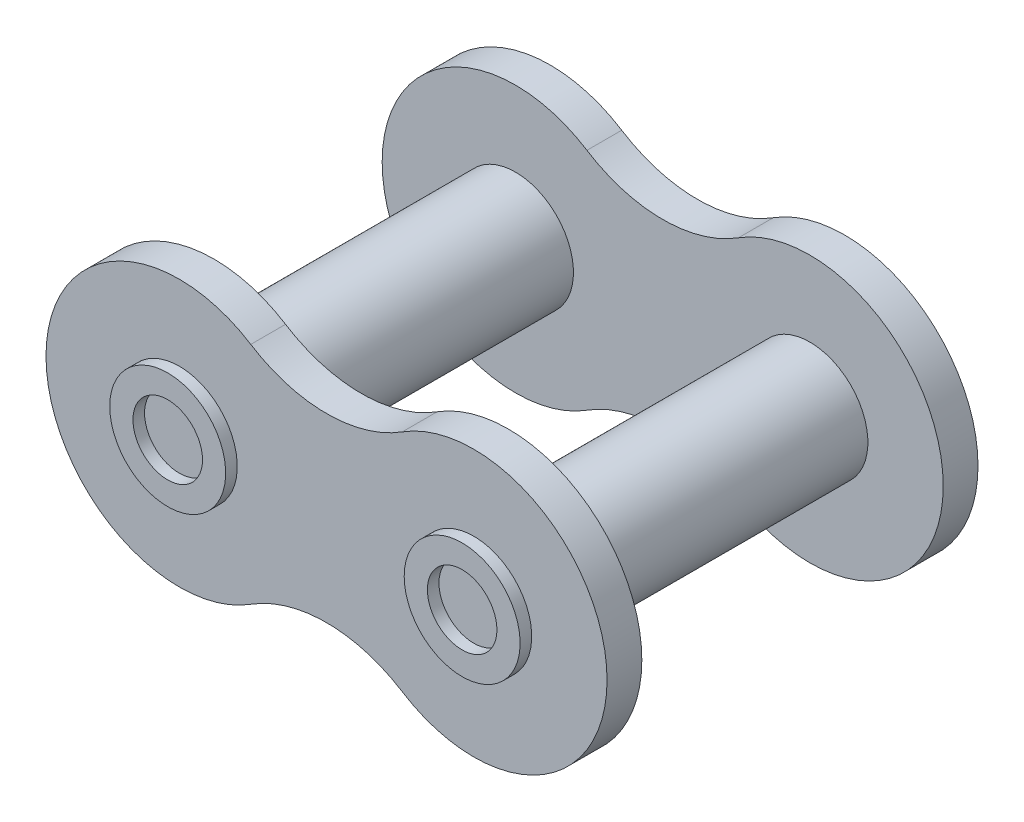
SolidWorks part; units mm, degrees
note: The reader was unsure of these and kept them because the rebuilt part matched: shared geometry of "Sketch1<5>".
ref_plane "Front Plane" through (0, 0, 0) normal (0, 0, 1) x (1, 0, 0)
ref_plane "Top Plane" through (0, 0, 0) normal (0, 1, 0) x (1, 0, 0)
ref_plane "Right Plane" through (0, 0, 0) normal (1, 0, 0) x (0, 0, -1)
sketch "Sketch1" plane through (0, 0, 0) normal (0, 0, 1) x (1, 0, 0)
  line L0 (0, 0) -> (-6.35, 0) construction
  line L1 (0, 0) -> (0, 10) construction
  circle A0 centre (-6.35, 0) radius 2.5
  circle A1 centre (6.35, 0) radius 2.5
  arc A2 (-3.2677, 4.854) -> (-3.2677, -4.854) centre (-6.35, 0) ccw
  arc A3 (3.2677, 4.854) -> (3.2677, -4.854) centre (6.35, 0) cw
  arc A4 (-3.2677, 4.854) -> (3.2677, 4.854) centre (0, 10) ccw
  arc A5 (-3.2677, -4.854) -> (3.2677, -4.854) centre (0, -10) cw
  circle A6 centre (-6.35, 0) radius 5.75 construction
  dimension "D2" = 5
  dimension "D3" = 5.75
  dimension "D1" = 12.7
  dimension "D4" = 10
extrude "Boss-Extrude3" add sketch "Sketch1" along normal mid plane 13 contours A1 | A0
extrude "Boss-Extrude7" add sketch "Sketch1<5>" against normal blind 1.5 from offset 6.5 contours A2 A5 A3 A4 offset against normal yes
sketch "Sketch1<5>" plane through (0, 0, 0) normal (0, 0, 1) x (1, 0, 0) same geometry as "Sketch1"
mirror "Mirror1" about plane through (0, 0, 0) normal (0, 0, 1) of "Boss-Extrude7"
sketch "Sketch2" plane through (0, 0, 0) normal (0, 0, 1) x (1, 0, 0)
  line L0 (0, 0) -> (0, 3.9042) construction
  circle A0 centre (-6.35, 0) radius 2.5
  arc A1 (-3.2677, 4.854) -> (3.2677, 4.854) centre (0, 10) ccw construction
  circle A2 centre (6.35, 0) radius 2.5
  dimension "D1" = 5
extrude "Boss-Extrude8" add sketch "Sketch2" along normal offset from surface 0.5 and the other way offset from surface (8.5 mm away) 0.5 contours A0 | A2 up to face at (0, 0, 8) offset beyond the face yes other way up to face at (0, 0, -8)
sketch "Sketch3" plane through (0, 0, 8.5) normal (0, 0, 1) x (1, 0, 0)
  circle A2 centre (-6.35, 0) radius 1.5
  circle A3 centre (-6.35, 0) radius 1.5
  circle A5 centre (6.35, 0) radius 1.5
  circle A6 centre (6.35, 0) radius 1.5
  dimension "D1" = 1
  dimension "D2" = 1
extrude "Cut-Extrude1" cut sketch "Sketch3" against normal up to surface (0.5 mm away) up to face at (3.85, 0, 8)
sketch "Sketch4" plane through (0, 0, -8.5) normal (0, 0, -1) x (-1, 0, 0)
  circle A0 centre (6.35, 0) radius 1.5 construction
  circle A1 centre (6.35, 0) radius 1.5
  circle A2 centre (-6.35, 0) radius 1.5 construction
  circle A3 centre (-6.35, 0) radius 1.5
extrude "Cut-Extrude2" cut sketch "Sketch4" against normal up to surface (0.5 mm away) up to face at (8.85, 0, -8)
